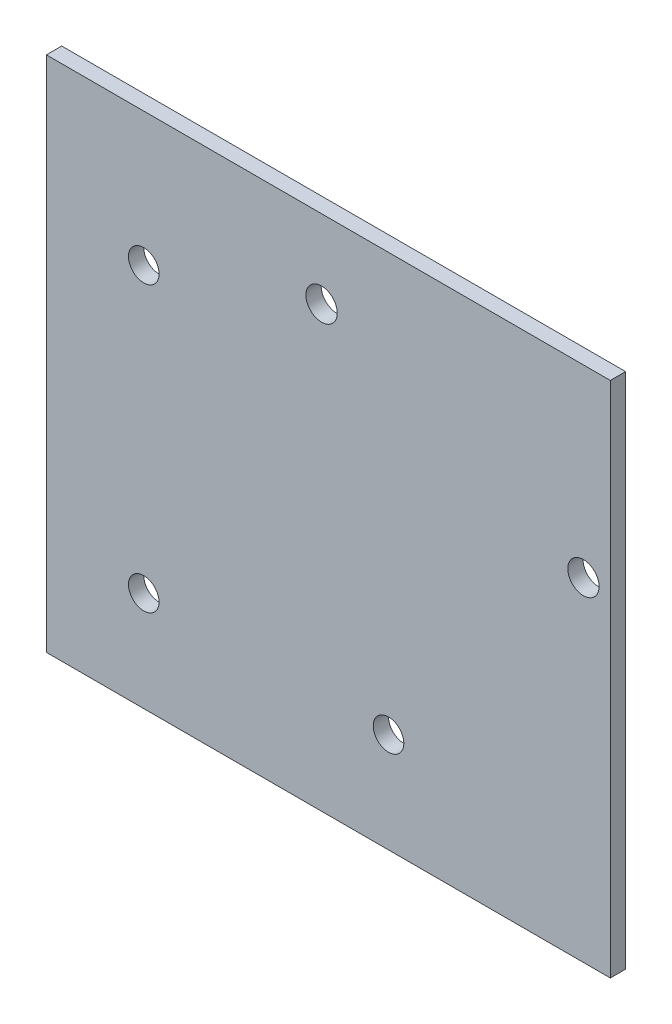
SolidWorks part; units mm, degrees
ref_plane "Front Plane" through (0, 0, 0) normal (0, 0, 1) x (1, 0, 0)
ref_plane "Top Plane" through (0, 0, 0) normal (0, 1, 0) x (1, 0, 0)
ref_plane "Right Plane" through (0, 0, 0) normal (1, 0, 0) x (0, 0, -1)
sketch "Sketch1" plane through (0, 0, 0) normal (0, 0, 1) x (1, 0, 0)
  line L0 (100.4021, 128.27) -> (100.4021, 179.07) construction
  line L1 (122.2369, 204.6053) -> (5.1872, 204.6053)
  line L2 (122.2369, 204.6053) -> (122.2369, 97.1939)
  line L3 (122.2369, 97.1939) -> (5.1872, 97.1939)
  line L4 (5.1872, 204.6053) -> (5.1872, 97.1939)
  line L5 (100.4021, 179.07) -> (49.6021, 179.07) construction
  line L6 (49.6021, 179.07) -> (49.6021, 128.27) construction
  circle A0 centre (25.4, 117.9286) radius 3.175
  circle A1 centre (25.4, 176.8929) radius 3.175
  circle A2 centre (76.2, 117.9286) radius 3.175
  circle A3 centre (116.6581, 166.37) radius 3.2512
  circle A4 centre (62.3021, 188.3578) radius 3.2512
  dimension "D1" = 6.35
  dimension "D4" = 6.5024
  dimension "D2" = 20.7346
  dimension "D3" = 20.2128
  dimension "D5" = 16.256
  dimension "D6" = 12.7
  dimension "D7" = 9.2878
  dimension "D8" = 12.7
  dimension "D9" = 5.5789
  dimension "D10" = 38.2353
extrude "Boss-Extrude1" add sketch "Sketch1" along normal blind 3.175
equation "\"80/20 to Center Hole\"= .64in"
equation "\"80/20 from Edge\"= 0.5in"
equation "\"D5@Sketch1\"=\"80/20 to Center Hole\""
equation "\"D6@Sketch1\"=\"80/20 from Edge\""
equation "\"D8@Sketch1\"=\"80/20 from Edge\""
